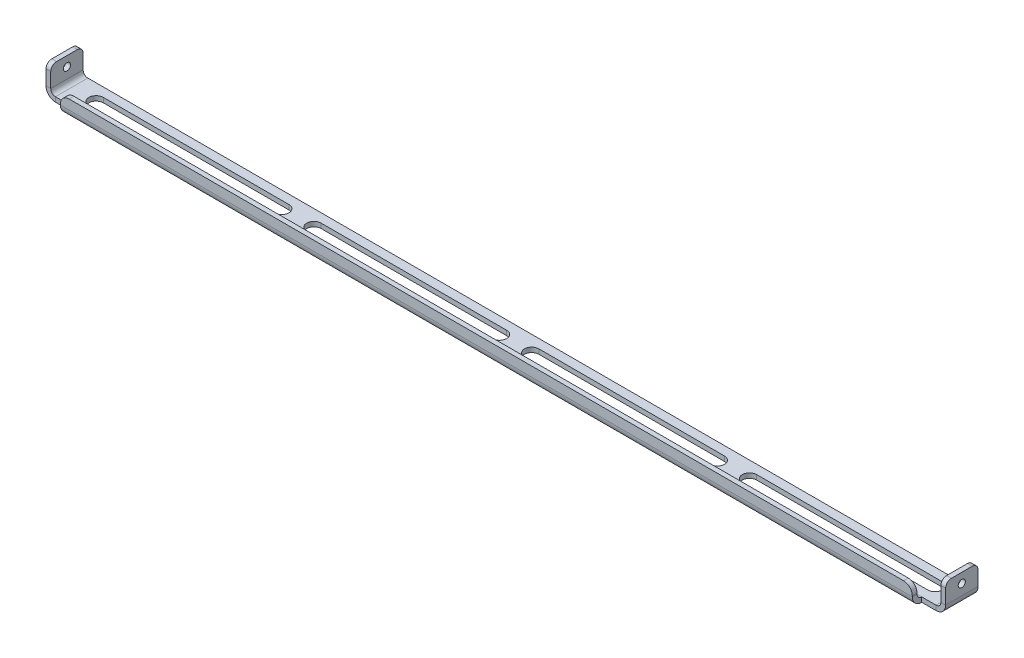
SolidWorks part; units mm, degrees
note: The reader was unsure of these and kept them because the rebuilt part matched: flange length of "Edge-Flange1", "Edge-Flange2".
ref_plane "Front Plane" through (0, 0, 0) normal (0, 0, 1) x (1, 0, 0)
ref_plane "Top Plane" through (0, 0, 0) normal (0, 1, 0) x (1, 0, 0)
ref_plane "Right Plane" through (0, 0, 0) normal (1, 0, 0) x (0, 0, -1)
sketch "Sketch1" plane through (0, 0, 0) normal (0, 1, 0) x (1, 0, 0)
  line L1 (0, 0) -> (312.6632, 0)
  line L2 (0, 0) -> (0, 11.25)
  line L3 (0, 11.25) -> (312.6632, 11.25)
  line L4 (312.6632, 0) -> (312.6632, 11.25)
  dimension "D1" = 11.25
  dimension "D2" = 312.6632
base flange "Base-Flange1" sketch "Sketch1" thickness 1.65 reverse thickness direction no parameters "D1"=1.65
edge flange "Edge-Flange1" sketch "Sketch6" flange profiles "Sketch6", "Sketch8" flange angle 90 flange length 8.75 flange position material inside bend radius 1.65 thickness 1.65 relief rectangular parameters "D1"=0.4, "D6"=10, "D8"=1
sketch "Sketch6" plane through (0, 0, 0) normal (-1, 0, 0) x (0, 0, 1)
  line L0 (-11.25, 0) -> (0, 0) construction
  line L1 (-11.25, 0) -> (0, 0)
  line L2 (-11.25, 0) -> (-11.25, 8.75)
  line L3 (-11.25, 8.75) -> (0, 8.75)
  line L4 (0, 8.75) -> (0, 0)
sketch "Sketch8" plane through (312.6632, 0, 0) normal (1, 0, 0) x (0, 0, -1)
  line L0 (0, 0) -> (11.25, 0) construction
  line L1 (0, 0) -> (11.25, 0)
  line L2 (0, 0) -> (0, 8.75)
  line L3 (0, 8.75) -> (11.25, 8.75)
  line L4 (11.25, 8.75) -> (11.25, 0)
bend "EdgeBend1" bend radius 1.65 bend angle 90 parameters "D5"=1
bend "EdgeBend2" bend radius 1.65 bend angle 90 parameters "D5"=3
sketch "Sketch9" plane through (0, 0, 0) normal (-1, 0, 0) x (0, 0, 1)
  line L0 (-5.625, 8.75) -> (-5.625, 5.375) construction
  line L1 (0, 8.75) -> (-11.25, 8.75) construction
  dimension "D1" = 3.375
sketch "Sketch13" plane through (312.6632, 0, 0) normal (1, 0, 0) x (0, 0, -1)
  line L0 (5.625, 8.75) -> (5.625, 5.375) construction
hole_wizard "Tap Drill for M3x0.5 Tap1" positions "3DSketch1" profile "Sketch14" hole size "M3x0.5" standard "ANSI Metric" end condition up to next
sketch3d "3DSketch1"
  point P0 (312.6632, 5.375, -5.625)
  point P3 (0, 5.375, -5.625)
sketch "Sketch14" plane through (312.6632, 5.375, -5.625) normal (0, 1, 0) x (0, 0, -1)
  line L0 (0, 0) -> (0, 1.65)
  line L1 (0, 1.65) -> (1.25, 1.65)
  line L2 (1.25, 1.65) -> (1.25, 0)
  line L5 (1.25, 0) -> (0, 0)
  line L11 (0, -6.35) -> (0, 107.95) construction
  dimension "Thru Hole Dia." = 2.5
  dimension "Thru Hole Depth" = 1.65
fillet "Fillet1" radius 2 4 edges at (311.8382, 8.75, 0) (311.8382, 8.75, -11.25) (0.825, 8.75, -11.25) (0.825, 8.75, 0)
sketch "Sketch15" plane through (0, 0, 0) normal (0, 1, 0) x (1, 0, 0)
  line L0 (11.8, 5.625) -> (76.3, 5.625) construction
  line L1 (11.8, 8.125) -> (76.3, 8.125)
  line L2 (11.8, 3.125) -> (76.3, 3.125)
  line L3 (87.49, 5.625) -> (151.99, 5.625) construction
  line L4 (87.49, 8.125) -> (151.99, 8.125)
  line L5 (87.49, 3.125) -> (151.99, 3.125)
  line L6 (154.49, 5.625) -> (309.3632, 5.625) construction
  line L7 (163.18, 5.625) -> (227.68, 5.625) construction
  line L8 (309.3632, 11.25) -> (309.3632, 0) construction
  line L9 (163.18, 8.125) -> (227.68, 8.125)
  line L10 (163.18, 3.125) -> (227.68, 3.125)
  line L11 (238.87, 5.625) -> (303.37, 5.625) construction
  line L12 (238.87, 8.125) -> (303.37, 8.125)
  line L13 (238.87, 3.125) -> (303.37, 3.125)
  line L14 (3.3, 0) -> (3.3, 11.25) construction
  arc A0 (11.8, 8.125) -> (11.8, 3.125) centre (11.8, 5.625) ccw
  arc A1 (76.3, 3.125) -> (76.3, 8.125) centre (76.3, 5.625) ccw
  arc A2 (87.49, 8.125) -> (87.49, 3.125) centre (87.49, 5.625) ccw
  arc A3 (151.99, 3.125) -> (151.99, 8.125) centre (151.99, 5.625) ccw
  arc A4 (163.18, 8.125) -> (163.18, 3.125) centre (163.18, 5.625) ccw
  arc A5 (227.68, 3.125) -> (227.68, 8.125) centre (227.68, 5.625) ccw
  arc A6 (238.87, 8.125) -> (238.87, 3.125) centre (238.87, 5.625) ccw
  arc A7 (303.37, 3.125) -> (303.37, 8.125) centre (303.37, 5.625) ccw
  point P2 (44.05, 5.625)
  point P11 (119.74, 5.625)
  point P20 (195.43, 5.625)
  point P27 (271.12, 5.625)
  point P32 (9.3, 5.625)
  dimension "D1" = 4
  dimension "D3" = 2.5
  dimension "D2" = 6
  dimension "D4" = 64.5
extrude "Cut-Extrude1" cut sketch "Sketch15" against normal up to next normal cut yes
edge flange "Edge-Flange2" sketch "Sketch18" flange angle 90 flange length 5 flange position bend outside bend radius 1.65 thickness 1.65 relief rectangular parameters "D6"=10
sketch "Sketch18" plane through (0, 0, 0) normal (0, 0, 1) x (1, 0, 0)
  line L0 (3.3, 0) -> (309.3632, 0) construction
  line L1 (8.3, 0) -> (304.3632, 0)
  line L2 (8.3, 0) -> (8.3, 5)
  line L3 (8.3, 5) -> (304.3632, 5)
  line L4 (304.3632, 5) -> (304.3632, 0)
  line L5 (309.3632, 0) -> (309.3632, -1.65) construction
  line L6 (3.3, 0) -> (3.3, -1.65) construction
  dimension "D1" = 5
  dimension "D2" = 5
bend "EdgeBend3" bend radius 1.65 bend angle 90 parameters "D5"=4
fillet "Fillet2" radius 3 2 edges at (8.3, 5, 2.475) (304.3632, 5, 2.475)
sketch "Bend-Lines1" [suppressed] plane through (0, 0, 0) normal (0, 1, 0) x (1, 0, 0)
sketch "Bounding-Box1" [suppressed] plane through (0, 0, 0) normal (0, 1, 0) x (1, 0, 0)
fillet "Fillet3" [suppressed] radius 0.7112
sheet metal parameters "Sheet-Metal7" thickness 1.65 parameters "D1"=1.016
flat pattern "Flat-Pattern7" [suppressed]
sketch "Bend-Lines2" plane through (0, 0, 0) normal (0, 1, 0) x (1, 0, 0)
sketch3d "Bounding-Box2" [suppressed]
  line L0 (-66.195, 6.75, 0) -> (0, 6.75, 0) construction
  line L1 (-66.195, 0, 0) -> (0, 0, 0) construction
  line L2 (-66.195, 6.75, 0) -> (-66.195, 0, 0) construction
  line L3 (0, 6.75, 0) -> (0, 0, 0) construction
sheet metal parameters "Sheet-Metal8" thickness 1.65 parameters "D1"=1.016
flat pattern "Flat-Pattern7"
sketch "Bend-Lines2" plane through (0, 0, 0) normal (0, 1, 0) x (1, 0, 0)
  line L0 (0.8351, 6.75) -> (0.8351, 0) construction
  line L1 (0.8351, 6.75) -> (0.8351, 0) construction
  line L2 (65.3599, 0) -> (65.3599, 6.75) construction
  line L3 (65.3599, 0) -> (65.3599, 6.75) construction
sketch3d "Bounding-Box2" [suppressed]
  line L0 (72.2909, 6.75, 0) -> (-6.0959, 6.75, 0) construction
  line L1 (72.2909, 0, 0) -> (-6.0959, 0, 0) construction
  line L2 (72.2909, 6.75, 0) -> (72.2909, 0, 0) construction
  line L3 (-6.0959, 6.75, 0) -> (-6.0959, 0, 0) construction
bend of the flat pattern "Flatten-<EdgeBend1>1"
bend of the flat pattern "Flatten-<EdgeBend2>1"
sheet metal parameters "Sheet-Metal9" thickness 1.65 parameters "D1"=1.016
flat pattern "Flat-Pattern7" [suppressed]
sketch "Bend-Lines2" plane through (0, 0, 0) normal (0, 1, 0) x (1, 0, 0)
  line L0 (0.8351, 13) -> (0.8351, 0) construction
  line L1 (0.8351, 13) -> (0.8351, 0) construction
  line L2 (314.1649, 0) -> (314.1649, 13) construction
  line L3 (314.1649, 0) -> (314.1649, 13) construction
sketch3d "Bounding-Box2" [suppressed]
  line L0 (321.0959, 13, 0) -> (-6.0959, 13, 0) construction
  line L1 (321.0959, 0, 0) -> (-6.0959, 0, 0) construction
  line L2 (321.0959, 13, 0) -> (321.0959, 0, 0) construction
  line L3 (-6.0959, 13, 0) -> (-6.0959, 0, 0) construction
bend of the flat pattern "Flatten-<EdgeBend1>1"
bend of the flat pattern "Flatten-<EdgeBend2>1"
sketch "Sketch9-1" [suppressed] plane through (0.6541, -1.016, 0) normal (0, -1, 0) x (0, 0, 1)
  line L0 (-6.5, 6.75) -> (-6.5, 3.375) construction
  dimension "D1" = 3.375
sketch "Sketch13-1" [suppressed] plane through (314.3459, -1.016, 0) normal (0, -1, 0) x (0, 0, -1)
  line L0 (6.5, 6.75) -> (6.5, 3.375) construction
sheet metal parameters "Sheet-Metal11" thickness 1.65 parameters "D1"=1.016
flat pattern "Flat-Pattern7" [suppressed]
sketch "Bend-Lines2" plane through (0, 0, 0) normal (0, 1, 0) x (1, 0, 0)
  line L0 (1.5758, 11.7) -> (1.5758, 0) construction
  line L1 (1.5758, 11.7) -> (1.5758, 0) construction
  line L2 (311.0874, 0) -> (311.0874, 11.7) construction
  line L3 (311.0874, 0) -> (311.0874, 11.7) construction
sketch3d "Bounding-Box2" [suppressed]
  line L0 (320.0117, 11.7, 0) -> (-7.3485, 11.7, 0) construction
  line L1 (320.0117, 0, 0) -> (-7.3485, 0, 0) construction
  line L2 (320.0117, 11.7, 0) -> (320.0117, 0, 0) construction
  line L3 (-7.3485, 11.7, 0) -> (-7.3485, 0, 0) construction
bend of the flat pattern "Flatten-<EdgeBend1>1"
bend of the flat pattern "Flatten-<EdgeBend2>1"
sketch "Sketch9-2" plane through (1.4015, -1.75, 0) normal (0, -1, 0) x (0, 0, 1)
  line L0 (-5.85, 8.75) -> (-5.85, 5.375) construction
  dimension "D1" = 3.375
sketch "Sketch13-2" plane through (311.2617, -1.75, 0) normal (0, -1, 0) x (0, 0, -1)
  line L0 (5.85, 8.75) -> (5.85, 5.375) construction
sheet metal parameters "Sheet-Metal44" thickness 1.65 parameters "D1"=1.016
flat pattern "Flat-Pattern7" [suppressed]
sketch "Bend-Lines2" plane through (0, 0, 0) normal (0, 1, 0) x (1, 0, 0)
  line L0 (1.4857, 11.25) -> (1.4857, 0) construction
  line L1 (1.4857, 11.25) -> (1.4857, 0) construction
  line L2 (311.1775, 0) -> (311.1775, 11.25) construction
  line L3 (311.1775, 0) -> (311.1775, 11.25) construction
  line L4 (8.3, -1.8143) -> (304.3632, -1.8143) construction
  line L5 (8.3, -1.8143) -> (304.3632, -1.8143) construction
sketch3d "Bounding-Box2" [suppressed]
  line L0 (320.0917, 11.25, 0) -> (-7.4285, 11.25, 0) construction
  line L1 (320.0917, -6.9785, 0) -> (-7.4285, -6.9785, 0) construction
  line L2 (320.0917, 11.25, 0) -> (320.0917, -6.9785, 0) construction
  line L3 (-7.4285, 11.25, 0) -> (-7.4285, -6.9785, 0) construction
bend of the flat pattern "Flatten-<EdgeBend1>1"
bend of the flat pattern "Flatten-<EdgeBend2>1"
bend of the flat pattern "Flatten-<EdgeBend3>1"
sketch "Sketch9-2" plane through (1.3215, -1.65, 0) normal (0, -1, 0) x (0, 0, 1)
  line L0 (-5.625, 8.75) -> (-5.625, 5.375) construction
  dimension "D1" = 3.375
sketch "Sketch13-2" plane through (311.3417, -1.65, 0) normal (0, -1, 0) x (0, 0, -1)
  line L0 (5.625, 8.75) -> (5.625, 5.375) construction
equation "\"itx-side-length\"= 6.7in"
equation "\"modular-cable-clearance\"= 30mm"
equation "\"right-angle-c14-clearance\"= 23mm"
equation "\"sfx-length\"= 100mm"
equation "\"spine-length\"= \"itx-side-length\" + \"modular-cable-clearance\" + \"sfx-length\" + \"right-angle-c14-clearance\""
equation "\"D2@Sketch1\" = 315 - 2 * \"reinforcement-thickness\""
equation "\"reinforcement-thickness\"= 1.1684mm"
